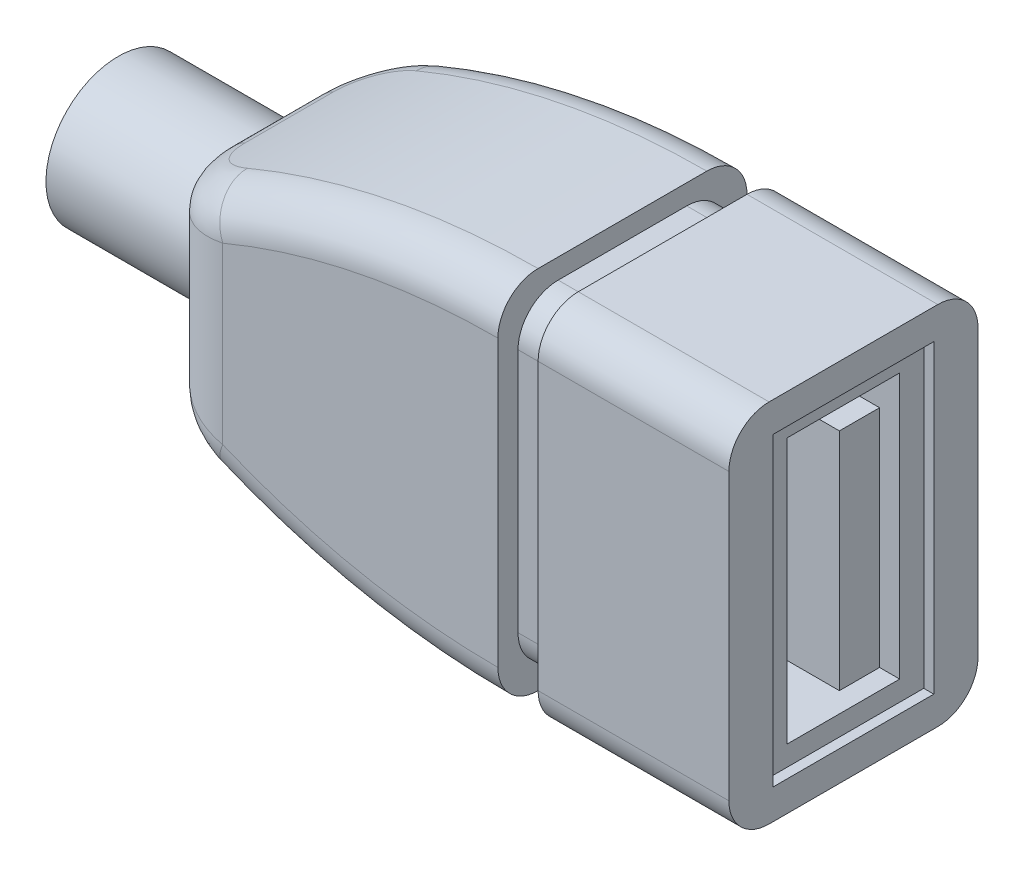
SolidWorks part; units mm, degrees
ref_plane "Front Plane" through (0, 0, 0) normal (0, 0, 1) x (1, 0, 0)
ref_plane "Top Plane" through (0, 0, 0) normal (0, 1, 0) x (1, 0, 0)
ref_plane "Right Plane" through (0, 0, 0) normal (1, 0, 0) x (0, 0, -1)
sketch "Sketch1" plane through (0, 0, 0) normal (0, 0, 1) x (1, 0, 0)
  line L0 (-14.6, 4.65) -> (-14.6, -4.65)
  line L2 (14.6, -9.1) -> (14.6, 9.1)
  line L5 (14.6, -9.1) -> (-14.6, 9.1) construction
  line L6 (14.6, 9.1) -> (-14.6, -9.1) construction
  line L7 (3.1, 9.1) -> (14.6, 9.1)
  line L8 (3.1, -9.1) -> (14.6, -9.1)
  arc A0 (3.1, 9.1) -> (-14.6, 4.65) centre (3.1, -28.3261) ccw
  arc A1 (3.1, -9.1) -> (-14.6, -4.65) centre (3.1, 28.3261) cw
  point P0 (0, 0)
  point P6 (-14.6, 4.65)
  point P7 (-14.6, -4.65)
  point P8 (3.1, 9.1)
  point P9 (3.1, -9.1)
  dimension "D1" = 29.2
  dimension "D2" = 18.2
  dimension "D3" = 9.3
  dimension "D4" = 4.45
  dimension "D5" = 11.5
  dimension "D6" = 11.5
extrude "Boss-Extrude1" add sketch "Sketch1" along normal blind 12.4
sketch "Sketch2" plane through (-14.6, 0, 0) normal (-1, 0, 0) x (0, 0, 1)
  line L0 (12.4, 4.65) -> (12.4, -4.65) construction
  circle A0 centre (6.2, 0) radius 3.6
  dimension "D2" = 7.2
  dimension "D1" = 6.2
extrude "Boss-Extrude2" add sketch "Sketch2" along normal blind 7.4
fillet "Fillet3" radius 4 1 edges at (-14.6, 0, 12.4) type face fillet first side face at (-14.6, -3.6, 6.2) second side face at (0.9415, 0, 12.4)
fillet "Fillet4" radius 4 1 edges at (-14.6, 0, 0) type face fillet first side face at (-14.6, 0, 4.6333) second side face at (0.9415, 0, 0)
fillet "Fillet5" radius 2 1 edges at (-14.6, -4.65, 6.2) type face fillet first side face at (-14.6, -3.9374, 6.2) second side face at (-7.7314, -6.8332, 6.3153)
fillet "Fillet6" radius 2 1 edges at (-14.6, 4.65, 6.2) type face fillet first side face at (-14.6, 3.9374, 6.2) second side face at (-7.7314, 6.8332, 6.0847)
sketch "Sketch3" plane through (0, 0, 12.4) normal (0, 0, 1) x (1, 0, 0)
  line L0 (14.6, -9.1) -> (3.1, -9.1) construction
  line L1 (3.1, 9.1) -> (5.1, 9.1)
  line L2 (3.1, 9.1) -> (3.1, -9.1)
  line L3 (3.1, -9.1) -> (5.1, -9.1)
  line L4 (5.1, 9.1) -> (5.1, -9.1)
  dimension "D1" = 2
extrude "Cut-Extrude1" cut sketch "Sketch3" against normal blind 1
sketch "Sketch4" plane through (0, 0, 0) normal (0, 0, -1) x (-1, 0, 0)
  line L0 (-14.6, 9.1) -> (-3.1, 9.1) construction
  line L1 (-3.1, -9.1) -> (-5.1, -9.1)
  line L2 (-3.1, -9.1) -> (-3.1, 9.1)
  line L3 (-3.1, 9.1) -> (-5.1, 9.1)
  line L4 (-5.1, -9.1) -> (-5.1, 9.1)
  dimension "D1" = 2
extrude "Cut-Extrude2" cut sketch "Sketch4" against normal blind 1
sketch "Sketch5" plane through (0, 0, 12.4) normal (0, 0, 1) x (1, 0, 0)
  line L0 (5.1, 8.8321) -> (5.1, 7.1) construction
  line L1 (3.1, 9.1) -> (5.1, 9.1)
  line L2 (3.1, 9.1) -> (3.1, 8.1)
  line L3 (3.1, 8.1) -> (5.1, 8.1)
  line L4 (5.1, 9.1) -> (5.1, 8.1)
  line L5 (5.1, -7.1) -> (5.1, -8.8321) construction
  line L6 (3.1, -9.1) -> (5.1, -9.1)
  line L7 (3.1, -9.1) -> (3.1, -8.1)
  line L8 (3.1, -8.1) -> (5.1, -8.1)
  line L9 (5.1, -9.1) -> (5.1, -8.1)
  dimension "D1" = 1
  dimension "D2" = 1
extrude "Cut-Extrude3" cut sketch "Sketch5" against normal blind 14
fillet "Fillet8" radius 2 1 edges at (4.1, -8.1, 11.4) type face fillet first side face at (4.1, 0, 11.4) second side face at (4.1, -8.1, 6.2)
fillet "Fillet9" radius 2 1 edges at (4.1, -8.1, 1) type face fillet first side face at (4.1, 0, 1) second side face at (4.1, -8.1, 5.2)
fillet "Fillet10" radius 2 1 edges at (4.1, 8.1, 1) type face fillet first side face at (4.1, 1, 1) second side face at (4.1, 8.1, 6.2)
fillet "Fillet11" radius 2 1 edges at (4.1, 8.1, 11.4) type face fillet first side face at (4.1, 8.1, 7.2) second side face at (4.1, 1, 11.4)
sketch "Sketch6" plane through (14.6, 0, 0) normal (1, 0, 0) x (0, 0, -1)
  line L0 (0, -7.1) -> (0, 7.1) construction
  line L1 (-2.2, 7.6) -> (-10.2, 7.6)
  line L2 (-2.2, 7.6) -> (-2.2, -7.6)
  line L3 (-2.2, -7.6) -> (-10.2, -7.6)
  line L4 (-10.2, 7.6) -> (-10.2, -7.6)
  line L6 (-10.4, 9.1) -> (-2, 9.1) construction
  line L7 (-10.4, -9.1) -> (-2, -9.1) construction
  dimension "D1" = 8
  dimension "D2" = 2.2
  dimension "D3" = 1.5
  dimension "D4" = 1.5
extrude "Cut-Extrude4" cut sketch "Sketch6" against normal blind 0.5
sketch "Sketch7" plane through (14.1, 0, 0) normal (1, 0, 0) x (0, 0, -1)
  line L0 (-2.2, -7.6) -> (-2.2, 7.6) construction
  line L1 (-3.4, 6.6) -> (-9, 6.6)
  line L2 (-3.4, 6.6) -> (-3.4, -6.6)
  line L3 (-3.4, -6.6) -> (-9, -6.6)
  line L4 (-9, 6.6) -> (-9, -6.6)
  line L6 (-10.2, -7.6) -> (-2.2, -7.6) construction
  line L7 (-2.2, 7.6) -> (-10.2, 7.6) construction
  line L9 (-4.4, 5.6) -> (-6.4, 5.6)
  line L10 (-4.4, 5.6) -> (-4.4, -5.6)
  line L11 (-4.4, -5.6) -> (-6.4, -5.6)
  line L12 (-6.4, 5.6) -> (-6.4, -5.6)
  dimension "D1" = 5.6
  dimension "D2" = 1.2
  dimension "D3" = 1
  dimension "D4" = 1
  dimension "D5" = 1
  dimension "D6" = 1
  dimension "D7" = 1
  dimension "D8" = 2
extrude "Cut-Extrude5" cut sketch "Sketch7" against normal blind 9
